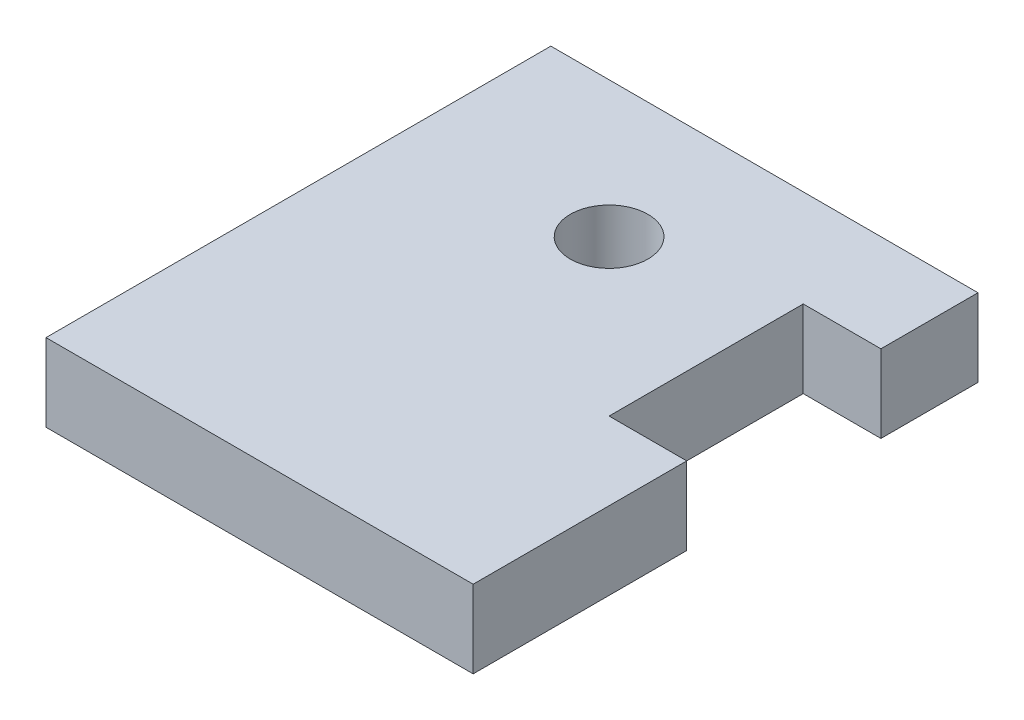
SolidWorks part; units mm, degrees
ref_plane "Front Plane" through (0, 0, 0) normal (0, 0, 1) x (1, 0, 0)
ref_plane "Top Plane" through (0, 0, 0) normal (0, 1, 0) x (1, 0, 0)
ref_plane "Right Plane" through (0, 0, 0) normal (1, 0, 0) x (0, 0, -1)
sketch "Sketch1" plane through (0, 0, 0) normal (0, 1, 0) x (1, 0, 0)
  line L9 (0, 0) -> (22, 0)
  line L17 (0, 0) -> (0, 26)
  line L18 (0, 26) -> (22, 26)
  line L19 (22, 0) -> (22, 11)
  line L20 (22, 21) -> (18, 21)
  line L22 (22, 11) -> (18, 11)
  line L23 (18, 21) -> (18, 11)
  line L24 (22, 21) -> (22, 26)
  circle A1 centre (10, 19) radius 2
  dimension "D6" = 7
  dimension "D7" = 4
  dimension "D1" = 26
  dimension "D2" = 22
  dimension "D3" = 4
  dimension "D4" = 5
  dimension "D5" = 10
  dimension "D8" = 10
extrude "Boss-Extrude1" add sketch "Sketch1" along normal blind 4
